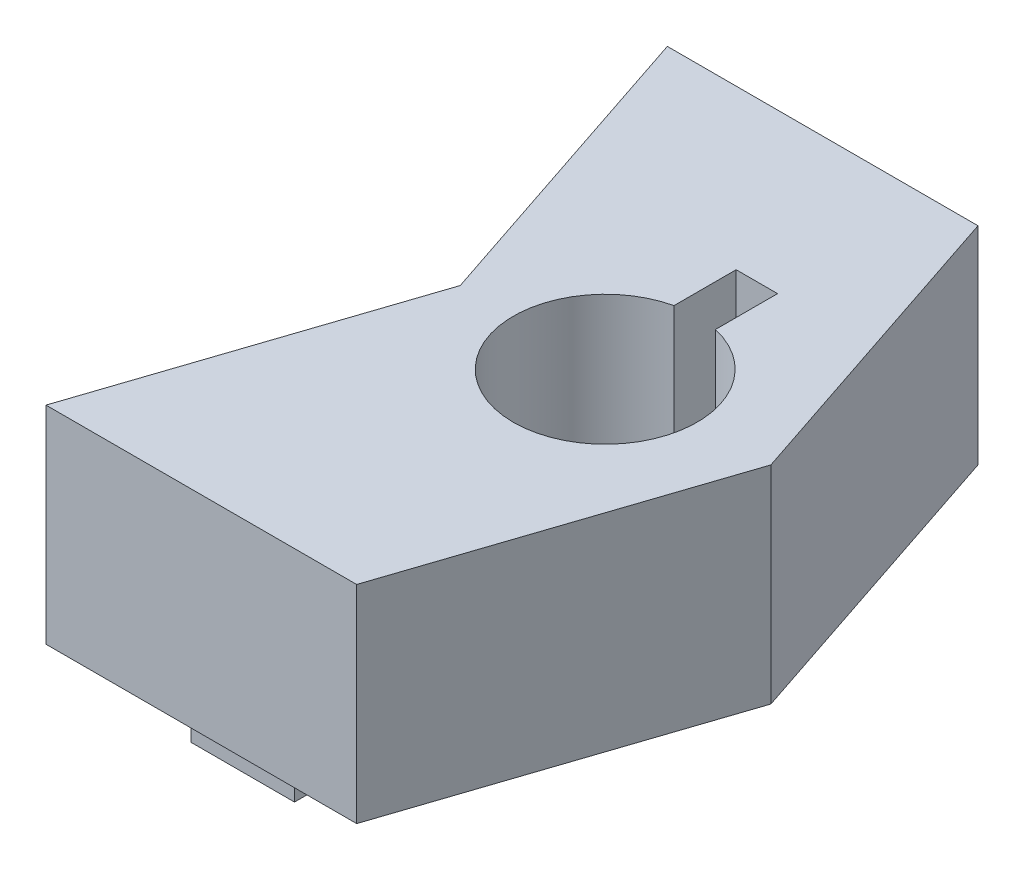
SolidWorks part; units mm, degrees
ref_plane "Front Plane" through (0, 0, 0) normal (0, 0, 1) x (1, 0, 0)
ref_plane "Top Plane" through (0, 0, 0) normal (0, 1, 0) x (1, 0, 0)
ref_plane "Right Plane" through (0, 0, 0) normal (1, 0, 0) x (0, 0, -1)
sketch "Sketch1" plane through (0, 0, 0) normal (0, 1, 0) x (1, 0, 0)
  line L0 (0, 0) -> (19.05, 0)
  line L1 (19.05, 0) -> (25.4, 19.05)
  line L2 (25.4, 19.05) -> (19.05, 38.1)
  line L3 (19.05, 38.1) -> (0, 38.1)
  line L4 (0, 38.1) -> (6.35, 19.05)
  line L5 (6.35, 19.05) -> (0, 0)
  dimension "D1" = 19.05
  dimension "D2" = 38.1
  dimension "D3" = 6.35
  dimension "D5" = 19.05
extrude "Boss-Extrude1" add sketch "Sketch1" along normal blind 12.7
sketch "Sketch2" plane through (0, 12.7, 0) normal (0, -1, 0) x (1, 0, 0)
  line L0 (25.4, -19.05) -> (6.35, -19.05) construction
  line L1 (6.35, -19.05) -> (0, 0) construction
  circle A0 centre (15.24, -19.05) radius 5.635
  dimension "D1" = 11.27
  dimension "D2" = 8.89
extrude "Haptic Motor Cutout" cut sketch "Sketch2" along normal blind 9.558 contours A0
sketch "Sketch3" plane through (0, 0, 0) normal (0, -1, 0) x (1, 0, 0)
  line L8 (16.51, -24.54) -> (13.97, -24.54)
  line L9 (16.51, -24.54) -> (16.51, -28.35)
  line L10 (13.97, -24.54) -> (13.97, -28.35)
  line L11 (16.51, -28.35) -> (13.97, -28.35)
  circle A3 centre (15.24, -19.05) radius 5.635 construction
  dimension "D1" = 2.54
  dimension "D2" = 3.81
extrude "Haptic Wire Cutout" cut sketch "Sketch3" against normal through all
ref_plane "MidPlane" through (0, 0, -19.05) normal (0, 0, -1) x (-1, 0, 0)
sketch "Sketch4" plane through (0, 0, 0) normal (0, -1, 0) x (1, 0, 0)
  line L0 (19.05, -38.1) -> (0, -38.1) construction
  line L1 (13.97, -36.83) -> (7.62, -36.83)
  line L2 (13.97, -36.83) -> (13.97, -34.29)
  line L3 (13.97, -34.29) -> (7.62, -34.29)
  line L4 (7.62, -36.83) -> (7.62, -34.29)
  line L5 (0, -6.985) -> (0, 6.985) construction
  dimension "D1" = 2.54
  dimension "D2" = 6.35
  dimension "D3" = 1.27
  dimension "D4" = 7.62
extrude "Pins" add sketch "Sketch4" along normal blind 2.032
mirror "Mirror1" about plane through (0, 0, -19.05) normal (0, 0, -1) of "Pins"
ref_point "Point1"
ref_axis "Axis1" through (0, 12.7, -38.1) along (0, 0, 1)
sketch "Sketch5" plane through (0, 12.7, 0) normal (0, 1, 0) x (1, 0, 0)
  line L0 (0, 38.1) -> (0, 0) construction
  line L1 (0, 19.05) -> (25.4, 19.05) construction
equation "\"Arrow Height\"= 1.5in"
equation "\"Button Height\"= 2in"
equation "\"Button Width\"= 4in"
equation "\"Haptic Diameter\"= 10mm"
equation "\"Haptic Thickness\"= 2.7mm"
equation "\"D2@Sketch1\"=\"Arrow Height\""
equation "\"D5@Sketch1\"=\"Arrow Height\"/2"
equation "\"D1@Sketch2\"=\"Haptic Diameter\"+.05in"
equation "\"D1@Haptic Motor Cutout\"=\"Haptic Thickness\" + .02+.25"
equation "\"D1@Haptic Wire Cutout\"=\"Haptic Thickness\"+.02+.25"
equation "\"Arrow Spacing\"= 1in"
equation "\"Arrow Width\"= 01in"
equation "\"Haptic Wire Angle\"= 63.43"
equation "\"Haptic Wire Width\"= .1in"
equation "\"Haptic Wire Height\"= .15in"
